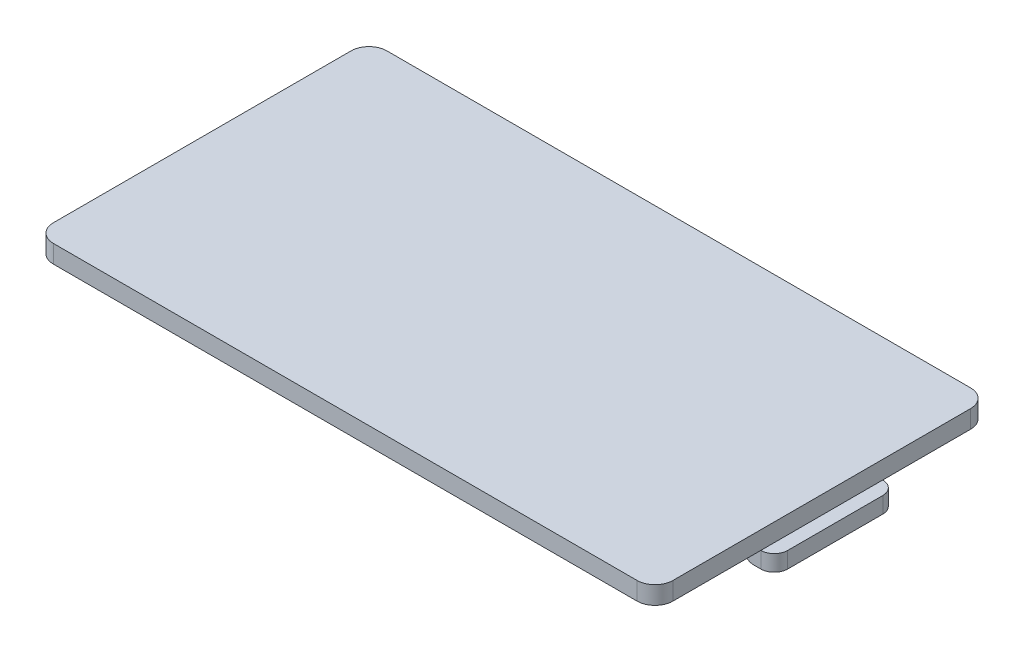
SolidWorks part; units mm, degrees
ref_plane "前视基准面" through (0, 0, 0) normal (0, 0, 1) x (1, 0, 0)
ref_plane "上视基准面" through (0, 0, 0) normal (0, 1, 0) x (1, 0, 0)
ref_plane "右视基准面" through (0, 0, 0) normal (1, 0, 0) x (0, 0, -1)
other "Configuration Table"
sketch "草图1" plane through (0, 0, 0) normal (0, 1, 0) x (1, 0, 0)
  line L0 (0, 0) -> (34.3, 0) construction
  line L1 (-34.55, 18.6) -> (34.55, 18.6)
  line L2 (-34.55, 18.6) -> (-34.55, -18.6)
  line L3 (-34.55, -18.6) -> (34.55, -18.6)
  line L4 (34.55, 18.6) -> (34.55, -18.6)
  line L5 (-34.55, 18.6) -> (34.55, -18.6) construction
  line L6 (-34.55, -18.6) -> (34.55, 18.6) construction
  line L8 (36.05, 6.8) -> (32.55, 6.8)
  line L9 (36.05, 6.8) -> (36.05, -6.8)
  line L10 (36.05, -6.8) -> (32.55, -6.8)
  line L11 (32.55, 6.8) -> (32.55, -6.8)
  line L12 (36.05, 6.8) -> (32.55, -6.8) construction
  line L13 (36.05, -6.8) -> (32.55, 6.8) construction
  circle A0 centre (-29.75, 7.1) radius 2.6
  circle A1 centre (-29.75, -7.1) radius 2.6
  point P0 (0, 0)
  point P18 (-34.55, 7.7774)
  dimension "D6" = 5.2
  dimension "D1" = 69.1
  dimension "D2" = 37.2
  dimension "D3" = 2
  dimension "D4" = 1.5
  dimension "D5" = 13.6
  dimension "D7" = 4.8
extrude "凸台-拉伸1" add sketch "草图1" along normal blind 2 contours L11 L8 L4 L1 L2 L3 L10 A0 A1 | L8 L11 L10 L4 | A1 | A0 region at (0.1404, 0, 0) region at (33.55, 0, 0) region at (-29.75, 0, -7.1) region at (-29.75, 0, 7.1)
extrude "凸台-拉伸2" add sketch "草图1<3>" against normal blind 1.8 contours L10 L9 L8 L4 | L8 L11 L10 L4 region at (35.3, 0, 0) region at (33.55, 0, 0)
sketch "草图1<3>" plane through (0, 0, 0) normal (0, 1, 0) x (1, 0, 0) same geometry as "草图1"
extrude "切除-拉伸1" cut sketch "草图1<5>" along normal blind 1 contours A1 | A0 region at (-29.75, 0, -7.1) region at (-29.75, 0, 7.1)
sketch "草图1<5>" plane through (0, 0, 0) normal (0, 1, 0) x (1, 0, 0) same geometry as "草图1"
fillet "圆角1" radius 2 4 edges at (34.55, 1, 18.6) (-34.55, 1, 18.6) (-34.55, 1, -18.6) (34.55, 1, -18.6)
fillet "圆角2" radius 1.5 2 edges at (36.05, -0.9, -6.8) (36.05, -0.9, 6.8)
fillet "圆角3" radius 1.2 1 edges at (32.55, -1.8, 0)
